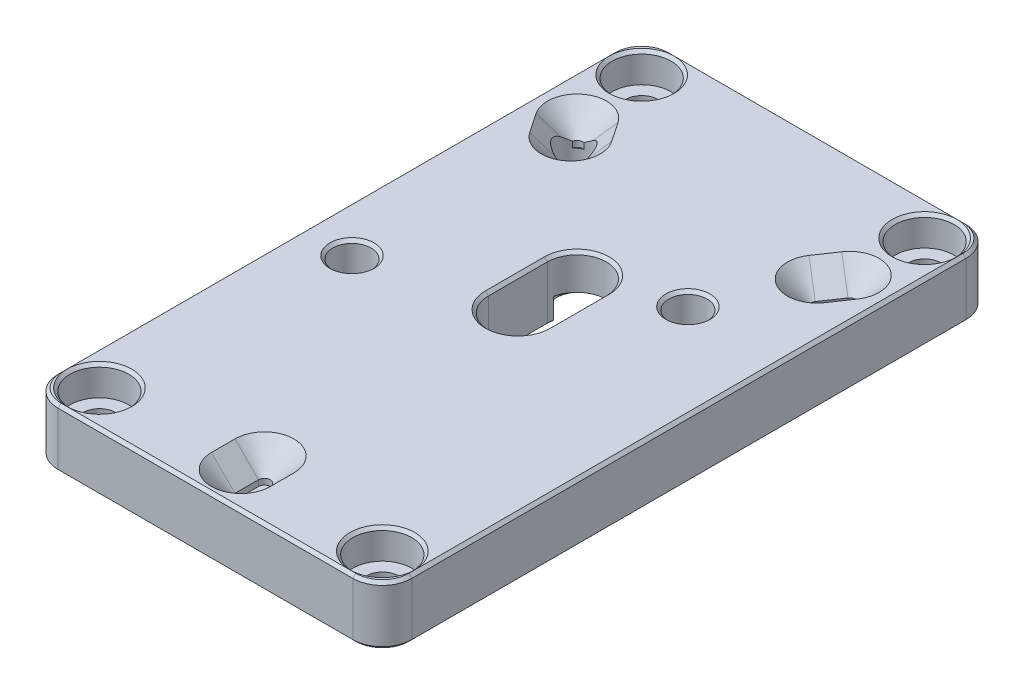
SolidWorks part; units mm, degrees
ref_plane "Front Plane" through (0, 0, 0) normal (0, 0, 1) x (1, 0, 0)
ref_plane "Top Plane" through (0, 0, 0) normal (0, 1, 0) x (1, 0, 0)
ref_plane "Right Plane" through (0, 0, 0) normal (1, 0, 0) x (0, 0, -1)
sketch "Sketch1" plane through (0, 0, 0) normal (0, 1, 0) x (1, 0, 0)
  line L1 (-30, 52) -> (30, 52)
  line L2 (-30, 52) -> (-30, -52)
  line L3 (-30, -52) -> (30, -52)
  line L4 (30, 52) -> (30, -52)
  line L5 (-30, 52) -> (30, -52) construction
  line L6 (-30, -52) -> (30, 52) construction
  point P0 (0, 0)
  dimension "D1" = 60
  dimension "D2" = 104
extrude "Boss-Extrude1" add sketch "Sketch1" along normal blind 10
sketch "Sketch10" plane through (0, 10, 0) normal (0, 1, 0) x (1, 0, 0)
  circle A0 centre (0, -44) radius 2.75 construction
  circle A1 centre (-22, 32.5) radius 2.75 construction
  circle A2 centre (22, 32.5) radius 2.75 construction
  circle A3 centre (0, -44) radius 2.75
  circle A4 centre (-22, 32.5) radius 2.75
  circle A5 centre (22, 32.5) radius 2.75
  circle A6 centre (0, 34) radius 15 construction
  circle A7 centre (0, -21.5) radius 15 construction
  circle A8 centre (0, 34) radius 15
  circle A9 centre (0, -21.5) radius 15
  circle A10 centre (0, 11) radius 1.85 construction
  circle A11 centre (0, 1) radius 1.85 construction
  circle A12 centre (0, 11) radius 1.85
  circle A13 centre (0, 1) radius 1.85
sketch "Sketch3" plane through (0, 10, 0) normal (0, 1, 0) x (1, 0, 0)
  line L0 (0, 0) -> (22, 32.5) construction
  line L1 (0, 0) -> (-22, 32.5) construction
  line L5 (0, 0) -> (0, -44) construction
  line L6 (-23.1211, 34.1562) -> (-20.8789, 30.8438) construction
  line L7 (-22.293, 34.7168) -> (-20.0508, 31.4043)
  line L8 (-23.9492, 33.5957) -> (-21.707, 30.2832)
  line L9 (23.1211, 34.1562) -> (20.8789, 30.8438) construction
  line L10 (23.9492, 33.5957) -> (21.707, 30.2832)
  line L11 (22.293, 34.7168) -> (20.0508, 31.4043)
  line L12 (0, -46) -> (0, -42) construction
  line L13 (-1, -46) -> (-1, -42)
  line L14 (1, -46) -> (1, -42)
  arc A0 (-22.293, 34.7168) -> (-23.9492, 33.5957) centre (-23.1211, 34.1562) ccw
  arc A1 (-21.707, 30.2832) -> (-20.0508, 31.4043) centre (-20.8789, 30.8438) ccw
  arc A2 (23.9492, 33.5957) -> (22.293, 34.7168) centre (23.1211, 34.1562) ccw
  arc A3 (20.0508, 31.4043) -> (21.707, 30.2832) centre (20.8789, 30.8438) ccw
  arc A4 (-1, -46) -> (1, -46) centre (0, -46) ccw
  arc A5 (1, -42) -> (-1, -42) centre (0, -42) ccw
  point P19 (-22, 32.5)
  point P25 (22, 32.5)
  point P32 (0, -44)
  dimension "D2" = 1
  dimension "D1" = 4
extrude "Cut-Extrude1" cut sketch "Sketch3" against normal blind 5
chamfer "Chamfer1" distance 4 angle 45 12 edges at (-22.8281, 10, -31.9394) (-20.3183, 10, -30.0157) (-23.6817, 10, -34.9843) (-21.1719, 10, -33.0606) (-1, 10, 44) (0, 10, 47) (0, 10, 41) (1, 10, 44) (21.1719, 10, -33.0606) (20.3183, 10, -30.0157) (23.6817, 10, -34.9843) (22.8281, 10, -31.9394)
sketch "Sketch5" plane through (0, 10, 0) normal (0, 1, 0) x (1, 0, 0)
  circle A2 centre (0, -21.5) radius 15 construction
  circle A3 centre (0, -21.5) radius 15
  circle A4 centre (0, 34) radius 15 construction
  circle A5 centre (0, 34) radius 15
extrude "Cut-Extrude3" cut sketch "Sketch5" against normal through all from offset 1.5 offset against normal yes
sketch "Sketch6" plane through (0, 10, 0) normal (0, 1, 0) x (1, 0, 0)
  line L8 (24, -46) -> (24, 46)
  line L9 (24, 46) -> (-24, 46)
  line L10 (-24, 46) -> (-24, -46)
  line L11 (-24, -46) -> (24, -46)
  line L12 (24, -46) -> (24, 46) construction
  line L13 (24, 46) -> (-24, 46) construction
  line L14 (-24, 46) -> (-24, -46) construction
  line L15 (-24, -46) -> (24, -46) construction
  dimension "D1" = 6
hole_wizard "CBORE for M5 SHCS1" positions "Sketch7" profile "Sketch8" counterbore size "M5" standard "ANSI Metric" end condition through all
sketch "Sketch7" plane through (0, 10, 0) normal (0, 1, 0) x (1, 0, 0)
  point P0 (-24, 46)
  point P3 (24, 46)
  point P6 (24, -46)
  point P9 (-24, -46)
sketch "Sketch8" plane through (-24, 10, -46) normal (1, 0, 0) x (0, 0, 1)
  line L0 (0, 0) -> (0, 10)
  line L1 (0, 10) -> (2.75, 10)
  line L3 (2.75, 10) -> (2.75, 5)
  line L4 (2.75, 5) -> (5, 5)
  line L5 (5, 5) -> (5, 0)
  line L7 (5, 0) -> (0, 0)
  line L11 (0, -6.35) -> (0, 107.95) construction
  dimension "Thru Hole Dia." = 5.5
  dimension "Thru Hole Depth" = 10
  dimension "C'Bore Dia." = 10
  dimension "C'Bore Depth" = 5
fillet "Fillet1" radius 5 4 edges at (30, 5, -52) (30, 5, 52) (-30, 5, 52) (-30, 5, -52)
sketch "Sketch9" plane through (0, 0, 0) normal (0, -1, 0) x (1, 0, 0)
  circle A0 centre (0, -19) radius 0.35
  circle A4 centre (0, -34) radius 15 construction
  dimension "D1" = 0.7
extrude "Boss-Extrude2" add sketch "Sketch9" against normal up to next
sketch "Sketch11" plane through (0, 0, 0) normal (0, -1, 0) x (1, 0, 0)
  circle A0 centre (0, 6.5) radius 0.35
  circle A1 centre (0, 21.5) radius 15 construction
  arc A2 (-0.35, -19.0041) -> (0.35, -19.0041) centre (0, -19) ccw construction
extrude "Boss-Extrude3" add sketch "Sketch11" against normal up to next contours A0
pattern_circular "CirPattern1" count 6 over 360 about axis through (0, 0, 21.5) along (0, 1, 0) of "Boss-Extrude3" reverse direction yes
pattern_circular "CirPattern2" count 6 over 360 about axis through (0, 0, -34) along (0, 1, 0) of "Boss-Extrude2" reverse direction yes
sketch "Sketch12" plane through (0, 10, 0) normal (0, 1, 0) x (1, 0, 0)
  line L0 (0, 1) -> (0, 11) construction
  line L1 (-5, 1) -> (-5, 11)
  line L2 (5, 1) -> (5, 11)
  arc A0 (-5, 1) -> (5, 1) centre (0, 1) ccw
  arc A1 (5, 11) -> (-5, 11) centre (0, 11) ccw
  point P4 (0, 6)
  dimension "D1" = 5
extrude "Cut-Extrude4" cut sketch "Sketch12" against normal through all
sketch "Sketch13" plane through (0, 0, 0) normal (0, -1, 0) x (1, 0, 0)
  line L0 (-29.5747, -105) -> (25.4932, -105) construction
  line L1 (25, -52) -> (-25, -52) construction
  line L2 (-25, -39.849) -> (17, -39.849) construction
  line L3 (-25, -39.849) -> (-25, 8.151) construction
  line L4 (-25, 8.151) -> (17, 8.151) construction
  line L5 (17, 8.151) -> (17, -39.849) construction
  line L6 (-25, 8.151) -> (17, -39.849) construction
  line L7 (14, -15.849) -> (-4, -15.849) construction
  line L8 (11.2484, 0.151) -> (11.2484, -31.849) construction
  point P6 (-22, -36.849)
  point P7 (-22, 5.151)
  point P10 (-4, -15.849)
  point P14 (14, -15.849)
  point P19 (11.2484, -15.849)
  dimension "D1" = 53
  dimension "D2" = 65.151
  dimension "D3" = 3
  dimension "D4" = 3
  dimension "D5" = 3
  dimension "D6" = 48
  dimension "D7" = 42
  dimension "D8" = 4
  dimension "D9" = 3
  dimension "D10" = 32
  dimension "D11" = 5.7516
sketch "Sketch14" plane through (0, 0, 0) normal (0, -1, 0) x (1, 0, 0)
  circle A0 centre (-4, -15.849) radius 4
  dimension "D1" = 8
extrude "Cut-Extrude5" cut sketch "Sketch14" against normal blind 4
sketch "Sketch15" plane through (0, 0, -52) normal (0, 0, -1) x (-1, 0, 0)
  line L0 (-25, 0) -> (25, 0) construction
  line L1 (0, 0) -> (0, -6) construction
  line L2 (8, 0) -> (-8, 0)
  arc A0 (8, 0) -> (-8, 0) centre (0, -6) ccw
  dimension "D1" = 10
  dimension "D2" = 6
extrude "Cut-Extrude6" cut sketch "Sketch15" against normal up to next
hole_wizard "CBORE for M3 SHCS1" positions "Sketch17" profile "Sketch18" counterbore size "M3" standard "ANSI Metric" end condition through all
sketch "Sketch17" plane through (0, 10, 0) normal (0, 1, 0) x (1, 0, 0)
  point P1 (-22, -5.151)
  point P5 (14, 15.849)
  point P13 (0, 0)
sketch "Sketch18" plane through (-22, 10, 5.151) normal (1, 0, 0) x (0, 0, 1)
  line L0 (0, 0) -> (0, 10)
  line L1 (0, 10) -> (1.7, 10)
  line L3 (1.7, 10) -> (1.7, 7)
  line L4 (1.7, 7) -> (3.25, 7)
  line L5 (3.25, 7) -> (3.25, 0)
  line L7 (3.25, 0) -> (0, 0)
  line L11 (0, -6.35) -> (0, 107.95) construction
  dimension "Thru Hole Dia." = 3.4
  dimension "Thru Hole Depth" = 10
  dimension "C'Bore Dia." = 6.5
  dimension "C'Bore Depth" = 7
chamfer "Chamfer2" distance 0.5 angle 45 34 edges at (0, 0, 52) (28.5355, 0, 50.5355) (-28.5355, 0, 50.5355) (30, 0, 0) (-30, 0, 0) (28.5355, 0, -50.5355) (-28.5355, 0, -50.5355) (16.5, 0, -52) (-16.5, 0, -52) (-5, 0, -6) (0, 0, 4) (-4.977, 0, -11.4789) (3.5345, 0, -14.5365) (5, 0, -6) (24, 10, 51) (-24, 10, 51) (-24, 10, -41) (24, 10, -41) (-5, 10, -6) (0, 10, 4) (0, 10, -16) (5, 10, -6) (-30, 10, 0) (-28.5355, 10, 50.5355) (-28.5355, 10, -50.5355) (0, 10, 52) (0, 10, -52) (28.5355, 10, 50.5355) (28.5355, 10, -50.5355) (30, 10, 0) (-22, 10, 8.401) (14, 10, -12.599) (-0.4737, 0, -17.7371) (-7.9993, 0, -15.924)
sketch "Sketch19" plane through (0, 10, 0) normal (0, 1, 0) x (1, 0, 0)
  circle A0 centre (-22, 32.5) radius 2.8
  dimension "D1" = 5.6
extrude "Cut-Extrude8" cut sketch "Sketch19" against normal up to surface (7 mm away) contours A0 up to face at (14, 3, -14.149)
sketch "Sketch20" plane through (0, 3, 0) normal (0, 1, 0) x (1, 0, 0)
  circle A0 centre (-22, 32.5) radius 1.6
  circle A1 centre (-22, 32.5) radius 2.8 construction
  dimension "D1" = 3.2
extrude "Cut-Extrude9" cut sketch "Sketch20" against normal through all
